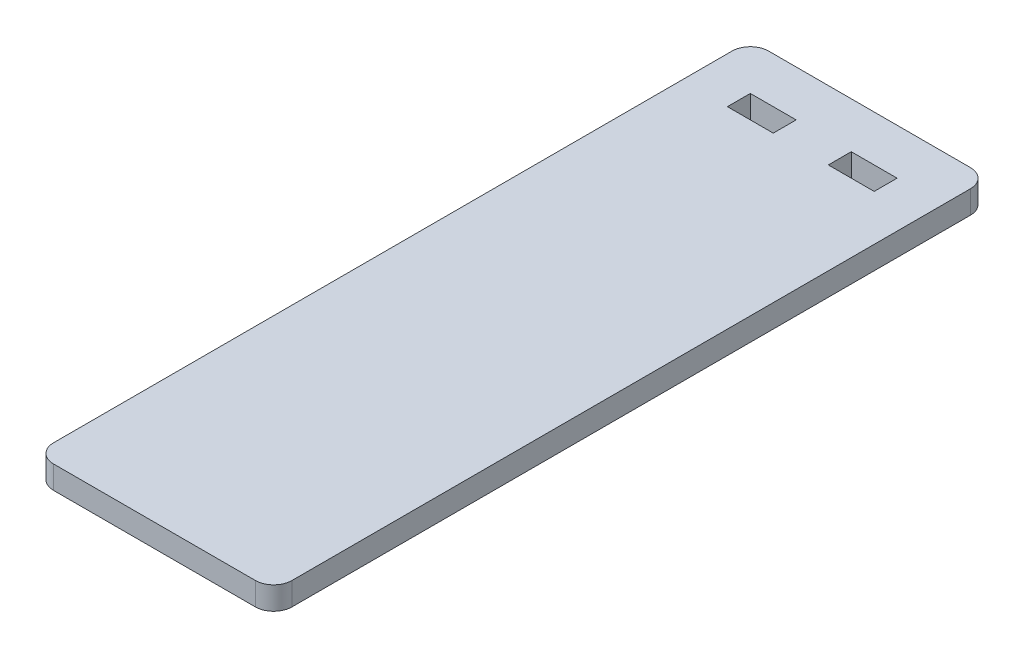
SolidWorks part; units mm, degrees
material "Acrylic (Medium-high impact)"
ref_plane "Front Plane" through (0, 0, 0) normal (0, 0, 1) x (1, 0, 0)
ref_plane "Top Plane" through (0, 0, 0) normal (0, 1, 0) x (1, 0, 0)
ref_plane "Right Plane" through (0, 0, 0) normal (1, 0, 0) x (0, 0, -1)
ref_plane "Plane1" through (0, 0, 0) normal (0, 1, 0) x (1, 0, 0)
sketch "Sketch1" plane through (0, 0, 0) normal (0, 1, 0) x (1, 0, 0)
  line L1 (-26.2811, -42.8338) -> (6.7489, -42.8338)
  line L2 (-26.2811, -42.8338) -> (-26.2811, 56.2162)
  line L3 (-26.2811, 56.2162) -> (6.7489, 56.2162)
  line L4 (6.7489, -42.8338) -> (6.7489, 56.2162)
  dimension "D1" = 99.05
  dimension "D2" = 33.03
extrude "Boss-Extrude1" add sketch "Sketch1" along normal blind 3.175
sketch "Sketch2" plane through (0, 3.175, 0) normal (0, 1, 0) x (1, 0, 0)
  line L0 (-26.2811, 56.2162) -> (-26.2811, -42.8338) construction
  line L1 (-5.9511, 46.6912) -> (0.3989, 46.6912)
  line L2 (-5.9511, 46.6912) -> (-5.9511, 49.8662)
  line L3 (-5.9511, 49.8662) -> (0.3989, 49.8662)
  line L4 (0.3989, 46.6912) -> (0.3989, 49.8662)
  line L5 (-19.9311, 46.6912) -> (-13.5811, 46.6912)
  line L6 (6.7489, 56.2162) -> (-26.2811, 56.2162) construction
  line L7 (6.7489, -42.8338) -> (6.7489, 56.2162) construction
  line L8 (-19.9311, 46.6912) -> (-19.9311, 49.8662)
  line L9 (-19.9311, 49.8662) -> (-13.5811, 49.8662)
  line L10 (-13.5811, 46.6912) -> (-13.5811, 49.8662)
  dimension "D1" = 6.35
  dimension "D2" = 3.175
  dimension "D3" = 6.35
  dimension "D4" = 6.35
  dimension "D5" = 3.175
  dimension "D6" = 6.35
  dimension "D7" = 6.35
  dimension "D8" = 6.35
  dimension "D9" = 7.63
extrude "Cut-Extrude1" cut sketch "Sketch2" against normal through all
fillet "Fillet1" radius 2.54 4 edges at (-26.2811, 1.5875, -56.2162) (6.7489, 1.5875, -56.2162) (6.7489, 1.5875, 42.8338) (-26.2811, 1.5875, 42.8338)
